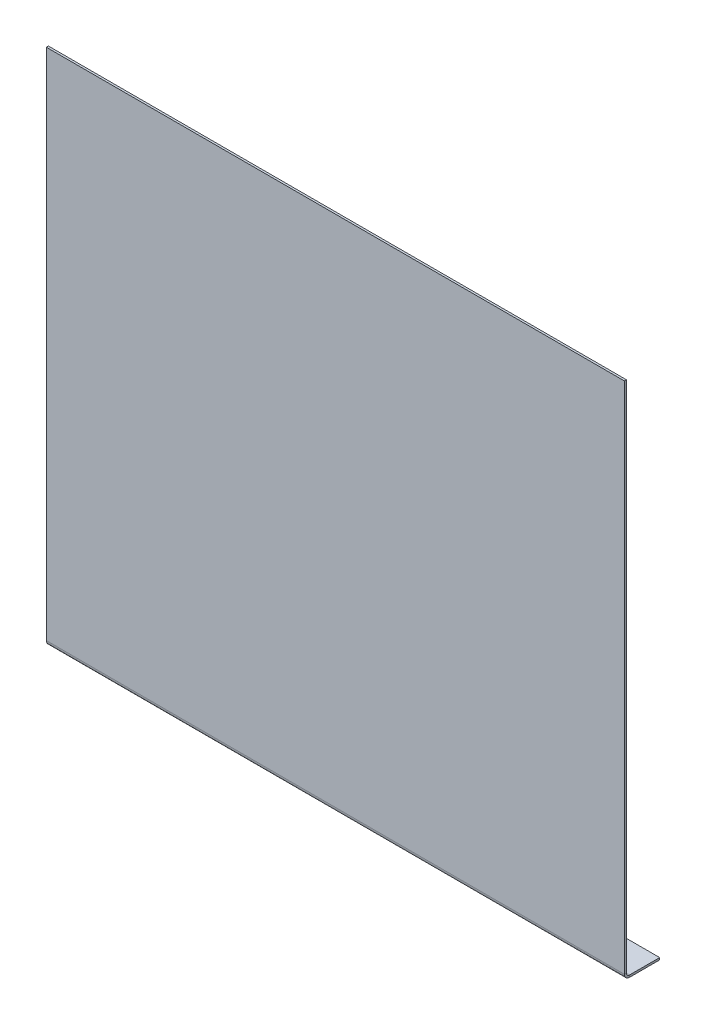
SolidWorks part; units mm, degrees
note: The reader was unsure of these and kept them because the rebuilt part matched: thickness of "Base-Flange1", "Edge-Flange1", "Sheet-Metal1", "Sheet-Metal5", "Sheet-Metal7"; flange length of "Edge-Flange1".
ref_plane "Front Plane" through (0, 0, 0) normal (0, 0, 1) x (1, 0, 0)
ref_plane "Top Plane" through (0, 0, 0) normal (0, 1, 0) x (1, 0, 0)
ref_plane "Right Plane" through (0, 0, 0) normal (1, 0, 0) x (0, 0, -1)
sketch "Sketch1" plane through (0, 0, 0) normal (0, 0, 1) x (1, 0, 0)
  line L0 (-15.5513, 182.3065) -> (195.3917, 49.2469) construction
  line L1 (-90, 70) -> (90, 70)
  line L2 (-90, 70) -> (-90, -90)
  line L3 (-90, -90) -> (90, -90)
  line L4 (90, 70) -> (90, -90)
  point P0 (0, 0)
  point P8 (0, 70)
  dimension "D1" = 90
  dimension "D2" = 180
  dimension "D3" = 70
base flange "Base-Flange1" sketch "Sketch1" thickness 0.64 reverse thickness direction no parameters "D1"=1
edge flange "Edge-Flange1" sketch "Sketch23" flange angle 90 flange length 11 flange position bend outside bend radius 1 thickness 0.64 relief rectangular parameters "D6"=10
sketch "Sketch23" plane through (0, -90, -0.64) normal (0, -1, 0) x (-1, 0, 0)
  line L2 (-90, 0) -> (-90, 10.36)
  line L3 (-90, 10.36) -> (90, 10.36)
  line L4 (90, 10.36) -> (90, 0)
  line L7 (90, 0) -> (-90, 0) construction
  line L8 (90, 0) -> (-90, 0)
bend "EdgeBend1" bend radius 1 bend angle 90 parameters "D5"=1
sketch "Sketch31" plane through (0, -91, 0) normal (0, 1, 0) x (1, 0, 0)
  line L1 (-90, 11) -> (90, 11) construction
  line L2 (90, 11) -> (90, 1.64) construction
  line L3 (0, 0) -> (0, 11) construction
  circle A6 centre (80, 6.5) radius 2.65
  circle A13 centre (-80, 6.5) radius 2.65
  dimension "D1" = 4.5
  dimension "D3" = 10
  dimension "D2" = 5.3
extrude "Cut-Extrude1" cut sketch "Sketch31" against normal through all normal cut yes
sketch "Bend-Lines1" [suppressed] plane through (0, 0, 0) normal (0, 1, 0) x (1, 0, 0)
sketch "Bounding-Box1" [suppressed] plane through (0, 0, 0) normal (0, 1, 0) x (1, 0, 0)
sheet metal parameters "Sheet-Metal1" thickness 0.64 parameters "D1"=1, "D7"=0.8128
flat pattern "Flat-Pattern1" [suppressed]
sketch "Bend-Lines2" plane through (0, 0, 0) normal (0, 1, 0) x (1, 0, 0)
sketch3d "Bounding-Box2" [suppressed]
  line L0 (-80, -90, 0) -> (80, -90, 0) construction
  line L1 (-80, 70, 0) -> (80, 70, 0) construction
  line L2 (-80, -90, 0) -> (-80, 70, 0) construction
  line L3 (80, -90, 0) -> (80, 70, 0) construction
sheet metal parameters "Sheet-Metal5" thickness 0.64 parameters "D1"=1, "D7"=0.8128
flat pattern "Flat-Pattern1"
sketch "Bend-Lines2" plane through (0, 0, 0) normal (0, 0, 1) x (1, 0, 0)
  line L0 (-90, -91.1046) -> (90, -91.1046) construction
  line L1 (-90, -91.1046) -> (90, -91.1046) construction
sketch3d "Bounding-Box2" [suppressed]
  line L0 (-90, -100.3964, 0) -> (90, -100.3964, 0) construction
  line L1 (-90, 70, 0) -> (90, 70, 0) construction
  line L2 (-90, -100.3964, 0) -> (-90, 70, 0) construction
  line L3 (90, -100.3964, 0) -> (90, 70, 0) construction
bend of the flat pattern "Flatten-<EdgeBend1>1"
sheet metal parameters "Sheet-Metal7" thickness 0.64 parameters "D1"=1, "D7"=0.8128
flat pattern "Flat-Pattern1"
sketch "Bend-Lines2" plane through (0, 0, 0) normal (0, 0, 1) x (1, 0, 0)
  line L0 (-90, -91.0367) -> (90, -91.0367) construction
  line L1 (-90, -91.0367) -> (90, -91.0367) construction
sketch3d "Bounding-Box2" [suppressed]
  line L0 (-90, -101.4335, 0) -> (90, -101.4335, 0) construction
  line L1 (-90, 70, 0) -> (90, 70, 0) construction
  line L2 (-90, -101.4335, 0) -> (-90, 70, 0) construction
  line L3 (90, -101.4335, 0) -> (90, 70, 0) construction
bend of the flat pattern "Flatten-<EdgeBend1>1"
